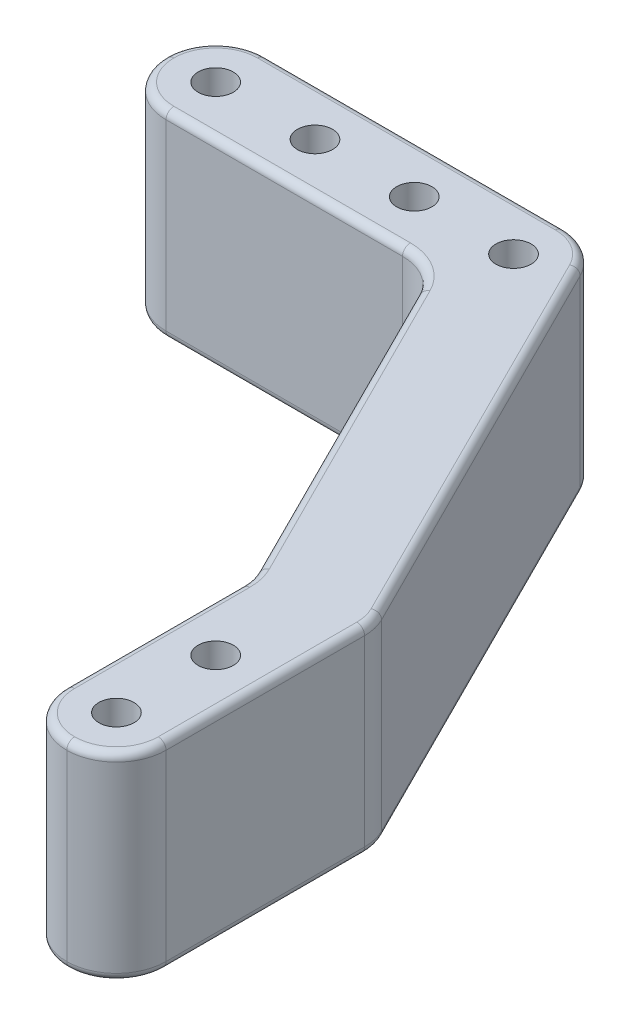
SolidWorks part; units mm, degrees
ref_plane "Front Plane" through (0, 0, 0) normal (0, 0, 1) x (1, 0, 0)
ref_plane "Top Plane" through (0, 0, 0) normal (0, 1, 0) x (1, 0, 0)
ref_plane "Right Plane" through (0, 0, 0) normal (1, 0, 0) x (0, 0, -1)
sketch "Sketch1" plane through (0, 0, 0) normal (0, 1, 0) x (1, 0, 0)
  line L0 (0, 0) -> (38.1, 0) construction
  line L1 (38.1, 0) -> (63.5, -50.8) construction
  line L2 (63.5, -50.8) -> (63.5, -76.2) construction
  line L3 (-6.35, 6.35) -> (-6.35, -6.35)
  line L4 (-6.35, -6.35) -> (34.1755, -6.35)
  line L5 (34.1755, -6.35) -> (57.15, -52.299)
  line L6 (57.15, -52.299) -> (57.15, -82.55)
  line L7 (57.15, -82.55) -> (69.85, -82.55)
  line L8 (69.85, -82.55) -> (69.85, -49.301)
  line L9 (69.85, -49.301) -> (42.0245, 6.35)
  line L10 (42.0245, 6.35) -> (-6.35, 6.35)
  circle A0 centre (0, 0) radius 2.25
  circle A1 centre (63.5, -76.2) radius 2.25
  circle A2 centre (63.5, -63.5) radius 2.25
  circle A3 centre (12.7, 0) radius 2.25
  circle A4 centre (25.4, 0) radius 2.25
  circle A5 centre (38.1, 0) radius 2.25
  dimension "D10" = 4.5
  dimension "D1" = 38.1
  dimension "D2" = 25.4
  dimension "D3" = 50.8
  dimension "D4" = 25.4
  dimension "D5" = 12.7
  dimension "D6" = 12.7
  dimension "D7" = 6.35
  dimension "D8" = 6.35
  dimension "D9" = 12.7
  dimension "D11" = 4
extrude "Boss-Extrude1" add sketch "Sketch1" along normal blind 25.4
fillet "Fillet1" radius 6.35 8 edges at (42.0245, 12.7, -6.35) (34.1755, 12.7, 6.35) (69.85, 12.7, 49.301) (57.15, 12.7, 52.299) (69.85, 12.7, 82.55) (57.15, 12.7, 82.55) (-6.35, 12.7, -6.35) (-6.35, 12.7, 6.35)
fillet "Fillet2" radius 1 28 edges at (-4.4901, 0, 4.4901) (-4.4901, 0, -4.4901) (19.05, 0, -6.35) (41.4384, 0, -5.4016) (56.4796, 0, 22.5602) (69.6801, 0, 49.3411) (69.85, 0, 63.5) (67.9901, 0, 80.6901) (59.0099, 0, 80.6901) (57.15, 0, 64.999) (56.9801, 0, 52.3391) (46.2051, 0, 30.4092) (33.5894, 0, 7.2984) (-4.4901, 25.4, 4.4901) (-4.4901, 25.4, -4.4901) (19.05, 25.4, -6.35) (41.4384, 25.4, -5.4016) (56.4796, 25.4, 22.5602) (69.6801, 25.4, 49.3411) (69.85, 25.4, 63.5) (67.9901, 25.4, 80.6901) (59.0099, 25.4, 80.6901) (57.15, 25.4, 64.999) (56.9801, 25.4, 52.3391) (46.2051, 25.4, 30.4092) (33.5894, 25.4, 7.2984) (15.1255, 0, 6.35) (15.1255, 25.4, 6.35)
